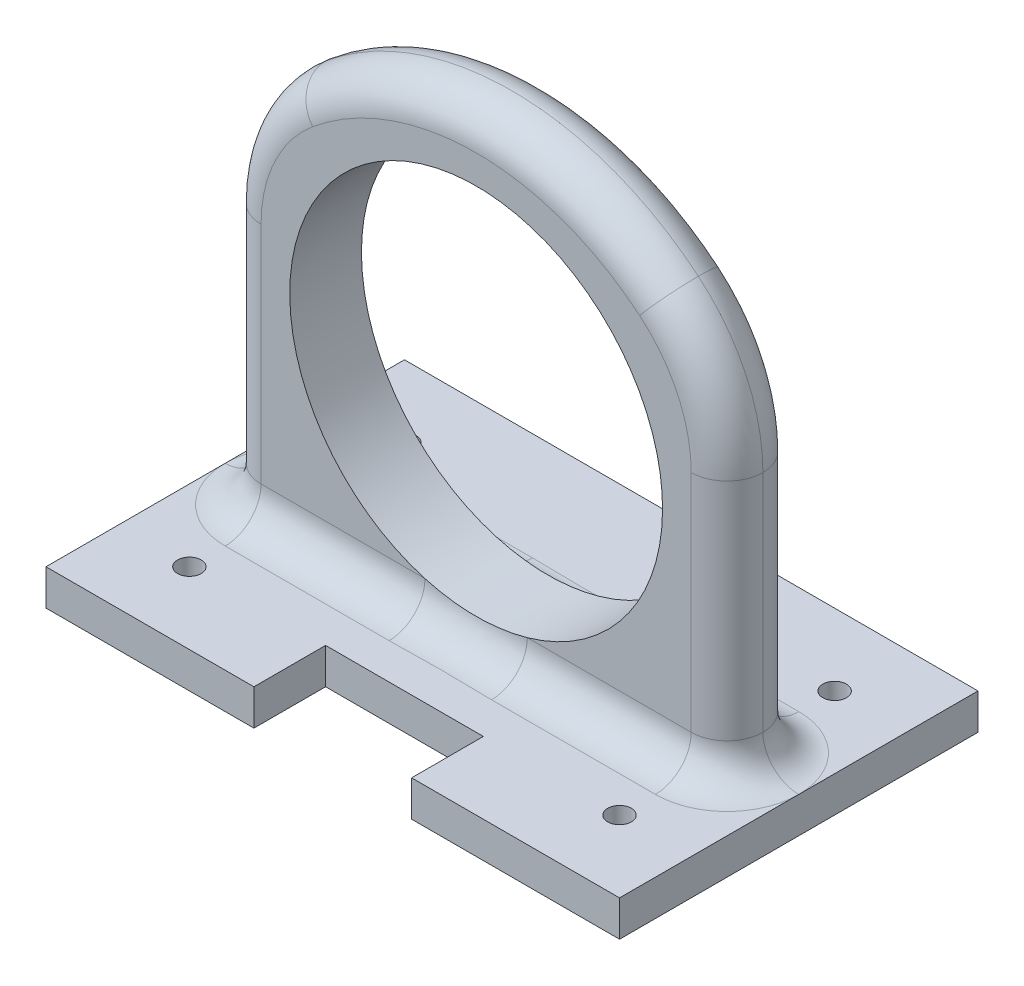
SolidWorks part; units mm, degrees
ref_plane "Front Plane" through (0, 0, 0) normal (0, 0, 1) x (1, 0, 0)
ref_plane "Top Plane" through (0, 0, 0) normal (0, 1, 0) x (1, 0, 0)
ref_plane "Right Plane" through (0, 0, 0) normal (1, 0, 0) x (0, 0, -1)
sketch "Sketch2" plane through (0, 0, 0) normal (0, 0, 1) x (1, 0, 0)
  line L0 (-35, 15) -> (35, 15)
  line L1 (-35, 35) -> (35, 35)
  line L2 (-35, 35) -> (-35, -35)
  line L3 (-35, -35) -> (35, -35)
  line L4 (35, 35) -> (35, -35)
  line L5 (-35, 35) -> (35, -35) construction
  line L6 (-35, -35) -> (35, 35) construction
  circle A0 centre (0, 0) radius 26
  arc A1 (-35, 15) -> (35, 15) centre (0, -5.625) cw
  dimension "D1" = 52
  dimension "D2" = 70
  dimension "D3" = 70
  dimension "D4" = 20
extrude "Boss-Extrude1" add sketch "Sketch2" along normal mid plane 10 contours L4 L1 L2 L3 A0 | A1 L0 A0 region at (-19.7944, 29.0153, 0) region at (-28.1184, 14.1398, 0)
sketch "Sketch3" plane through (0, -35, 0) normal (0, -1, 0) x (1, 0, 0)
  line L0 (38.5, 0) -> (-38.5, 0) construction
  line L1 (40, -25) -> (-40, -25)
  line L2 (40, -25) -> (40, 25)
  line L3 (40, 25) -> (-40, 25)
  line L4 (-40, -25) -> (-40, 25)
  line L5 (40, -25) -> (-40, 25) construction
  line L6 (40, 25) -> (-40, -25) construction
  circle A0 centre (-30, 15) radius 2
  circle A2 centre (30, 15) radius 2
  circle A3 centre (30, -15) radius 2
  circle A4 centre (-30, -15) radius 2
  point P0 (0, 0)
  point P12 (-34.0914, 16.7147)
  line M5 (35, -5) -> (35, 5)
  line M7 (-35, 5) -> (-35, -5)
  dimension "D5" = 4
  dimension "D9" = 4
  dimension "D1" = 50
  dimension "D2" = 80
  dimension "D3" = 10
  dimension "D4" = 10
  dimension "D6" = 30
  dimension "D7" = 60
  dimension "D10" = 10
  dimension "D11" = 10
extrude "Boss-Extrude2" add sketch "Sketch3" against normal blind 5 contours L4 L1 L2 L3 A3 A2 A0 A4 M7 M5 | A4 | A2 | A3 | A0 region at (0, -35, 0) region at (30, -35, 15) region at (30, -35, -15) region at (-30, -35, -15)
hole_wizard "Tap Drill for M4x0.7 Tap1" positions "3DSketch5" profile "Sketch7" hole size "M4x0.7" standard "ANSI Metric" end condition up to next
sketch3d "3DSketch5"
  point P0 (-30, -35, 15)
  point P3 (-30, -35, -15)
  point P6 (30, -35, 15)
  point P9 (30, -35, -15)
sketch "Sketch7" plane through (-30, -35, 15) normal (1, 0, 0) x (0, 0, -1)
  line L0 (0, 0) -> (0, 5)
  line L1 (0, 5) -> (1.65, 5)
  line L2 (1.65, 5) -> (1.65, 0)
  line L5 (1.65, 0) -> (0, 0)
  line L11 (0, -6.35) -> (0, 107.95) construction
  dimension "Thru Hole Dia." = 3.3
  dimension "Thru Hole Depth" = 5
fillet "Fillet3" radius 25 2 edges at (35, 15, 0) (-35, 15, 0)
fillet "Fillet4" radius 5 12 edges at (0, -30, -5) (0, -30, 5) (-35, -11.8096, -5) (-32.6385, 16.9875, -5) (35, -11.8096, -5) (32.6385, 16.9875, -5) (-35, -11.8096, 5) (35, -11.8096, 5) (32.6385, 16.9875, 5) (0, 35, -5) (-32.6385, 16.9875, 5) (0, 35, 5)
sketch "Sketch8" plane through (0, -30, 0) normal (0, 1, 0) x (1, 0, 0)
  line L0 (40, -25) -> (-40, -25) construction
  line L1 (-11, -15) -> (11, -15)
  line L2 (-11, -15) -> (-11, -25)
  line L3 (-11, -25) -> (11, -25)
  line L4 (11, -15) -> (11, -25)
  point P6 (0, -25)
  dimension "D1" = 22
  dimension "D2" = 10
extrude "Cut-Extrude1" cut sketch "Sketch8" against normal up to surface (5 mm away) up to face at (-30, -35, 13.35)
